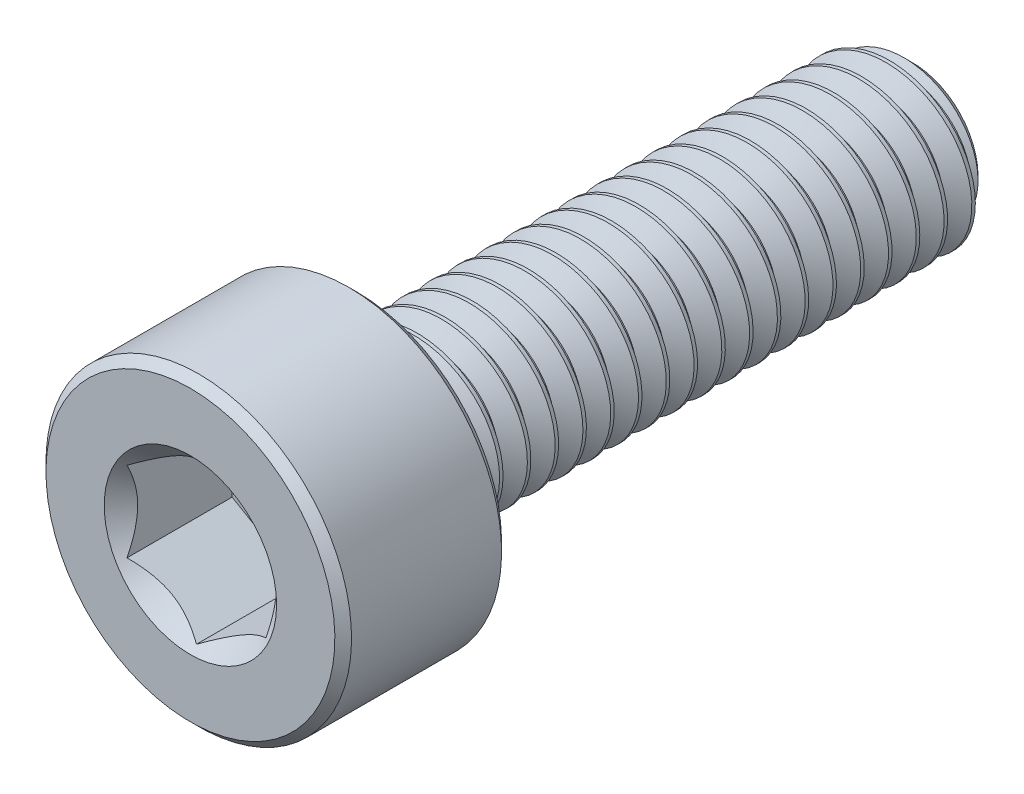
SolidWorks part; units mm, degrees
material "Alloy Steel"
ref_plane "Front Plane" through (0, 0, 0) normal (0, 0, 1) x (1, 0, 0)
ref_plane "Top Plane" through (0, 0, 0) normal (0, 1, 0) x (1, 0, 0)
ref_plane "Right Plane" through (0, 0, 0) normal (1, 0, 0) x (0, 0, -1)
sketch "Sketch1" plane through (0, 0, 0) normal (1, 0, 0) x (0, 0, -1)
  line L0 (-6.5, 0) -> (6.5, 0) construction
  line L1 (6.5, 0) -> (6.5, 1.1752) construction
  line L2 (6.5, 1.1752) -> (6.1752, 1.5) construction
  line L3 (6.1752, 1.5) -> (6.125, 1.5) construction
  line L4 (6.125, 1.5) -> (-3.5, 1.5) construction
  line L5 (-3.5, 1.5) -> (-3.5, 2.75) construction
  line L6 (-3.5, 2.75) -> (-6.5, 2.75) construction
  line L7 (-6.5, 2.75) -> (-6.5, 0) construction
  line L8 (6.5, 1.1752) -> (6.5, 1.5) construction
  line L9 (6.4688, 1.5541) -> (6.7188, 1.1211) construction
  line L10 (6.7188, 1.1211) -> (6.9687, 1.5541) construction
  line L11 (6.9687, 1.5541) -> (6.4688, 1.5541) construction
  line L12 (6.7188, 1.5541) -> (6.7188, 1.5) construction
  line L13 (6.7188, 1.1211) -> (6.7188, 1.1752) construction
  line L14 (6.6875, 1.1752) -> (6.75, 1.1752) construction
  line L15 (6.5, 1.5) -> (6.9375, 1.5) construction
  line L16 (6.4844, 1.5271) -> (6.9531, 1.5271) construction
  line L17 (6.5, 0) -> (6.5, -1.5) construction
  line L18 (-3.65, 2.75) -> (-3.5, 2.6) construction
  line L19 (-6.35, 2.75) -> (-6.5, 2.6) construction
  line L20 (-3.5, 1.5) -> (-3.5, 0) construction
  line L21 (-3.5, 0.75) -> (-0.1667, 0.75) construction
  line L22 (-0.1667, 0.75) -> (3.1667, 0.75) construction
  line L23 (3.1667, 0.75) -> (6.5, 0.75) construction
  line L24 (-0.1667, 0.75) -> (-0.1667, 1.5) construction
  line L25 (-0.1667, 1.5) -> (-0.1667, 2.75) construction
  line L26 (3.1667, 0.75) -> (3.1667, 2.75) construction
  point P0 (-6.5, 1.25)
  point P3 (5.25, 1.5)
  point P4 (0, 0)
  point P18 (3.1667, 1.5)
  point P22 (6.7188, 1.1752)
  point P24 (6.125, 1.5)
  point P25 (6.7188, 1.5)
  point P28 (6.7187, 1.5271)
  point P29 (5.25, -1.5)
  point P30 (-0.1667, 1.5)
  point P31 (-5, 2.75)
  point P37 (-4.025, 2.75)
  point P38 (-6.275, 2.75)
  point P45 (-0.1667, 0.75)
  point P46 (3.1667, 0.75)
  dimension "D2" = 0.0625
  dimension "D7" = 0.15
  dimension "D8" = 0.15
  dimension "D9" = 0.15
  dimension "D10" = 0.075
  dimension "D11" = 0.375
  dimension "Drive Size" = 2.5
  dimension "Head Diameter" = 5.5
  dimension "Head Height" = 3
  dimension "Thread Pitch" = 0.5
  dimension "Thread Dia" = 3
  dimension "Length" = 10
  dimension "D12" = 0.375
  dimension "D4" = 1.25
  dimension "D3" = 45
sketch "Sketch2" plane through (0, 0, 0) normal (1, 0, 0) x (0, 0, -1)
  line L0 (-6.5, 0) -> (-6.5, 2.6)
  line L1 (-6.35, 2.75) -> (-3.65, 2.75)
  line L2 (-3.5, 2.6) -> (-3.5, 1.65)
  line L4 (6.1752, 1.5) -> (6.5, 1.1752)
  line L5 (6.5, 1.1752) -> (6.5, 0)
  line L6 (-3.5, 2.75) -> (-6.5, 2.75) construction
  line L7 (6.5, 0) -> (-6.5, 0)
  line L8 (-6.35, 2.75) -> (-6.5, 2.6) construction
  line L10 (-6.35, 2.75) -> (-6.5, 2.6)
  line L14 (-3.65, 2.75) -> (-3.5, 2.6) construction
  line L16 (-3.65, 2.75) -> (-3.5, 2.6)
  line L17 (-3.5, 1.5) -> (-3.5, 2.75) construction
  line L19 (-3.35, 1.5) -> (6.1752, 1.5)
  line L20 (6.125, 1.5) -> (-3.5, 1.5) construction
  arc A1 (-3.5, 1.65) -> (-3.35, 1.5) centre (-3.35, 1.65) ccw
  dimension "D3" = 0.15
revolve "Revolve1" add sketch "Sketch2" angle 360 about L7
sketch "Sketch3" plane through (0, 0, 6.5) normal (0, 0, 1) x (1, 0, 0)
  line L1 (1.25, -0.7217) -> (1.25, 0.7217)
  line L2 (1.25, 0.7217) -> (0, 1.4434)
  line L3 (0, 1.4434) -> (-1.25, 0.7217)
  line L4 (-1.25, 0.7217) -> (-1.25, -0.7217)
  line L5 (-1.25, -0.7217) -> (0, -1.4434)
  line L6 (0, -1.4434) -> (1.25, -0.7217)
  circle A0 centre (0, 0) radius 1.25 construction
  circle A1 centre (0, 0) radius 2.75 construction
  circle A2 centre (0, 0) radius 2.75 construction
  circle A3 centre (0, 0) radius 1.4434 construction
  point P13 (0, 0)
  dimension "D1" = 2.8868
extrude "Cut-Extrude1" cut sketch "Sketch3" against normal offset from surface (2 mm away) 1 up to face at (0, 2.6, 3.5)
sketch "Sketch4" plane through (0, 0, 6.5) normal (0, 0, 1) x (1, 0, 0)
  circle A0 centre (0, 0) radius 1.5516
  dimension "D1" = 3.1033
extrude "Cut-Extrude2" cut sketch "Sketch4" against normal up to vertex (1.5 mm away) draft 45 up to point (0, 2.75, 5)
sketch "Sketch11" plane through (0, 0, 0) normal (1, 0, 0) x (0, 0, -1)
  line L0 (-6.5, 0) -> (6.5, 0) construction
  line L1 (-6.5, 0) -> (6.5, 0) construction
  line L2 (-1.625, 0) -> (-1.625, 1.5) construction
  line L3 (6.125, 1.5) -> (-3.5, 1.5) construction
  line L4 (4.625, 0) -> (4.625, 1.5) construction
  line L6 (6.5, 1.1752) -> (6.5, 1.5) construction
  point P2 (-1.625, 0)
  point P3 (4.625, 0)
  dimension "D1" = 1.875
  dimension "D2" = 1.875
sketch "Sketch6" plane through (0, 0, -6.5) normal (0, 0, -1) x (-1, 0, 0)
  circle A0 centre (0, 0) radius 1.5
curve "Helix/Spiral1" pitch 0.5 height 10.5 radius 1.5 centre (0, 0, -6.5) axis (0, 0, 1) start towards (0, 1, 0)
sketch "Sketch10" plane through (0, 0, 0) normal (1, 0, 0) x (0, 0, -1)
  line L0 (-3.35, -2.75) -> (-3.35, 2.75)
  line L5 (-6.5, 0) -> (6.5, 0) construction
  line L6 (-3.35, 1.5) -> (-3.35, -1.5) construction
  point P3 (-3.35, 0)
split "Split1" trim tools "Sketch10" bodies to split 106 resulting bodies 114 115
sketch "Sketch7" plane through (0, 0, 0) normal (1, 0, 0) x (0, 0, -1)
  line L0 (6.4844, 1.5271) -> (6.9531, 1.5271)
  line L1 (6.9531, 1.5271) -> (6.75, 1.1752)
  line L2 (6.75, 1.1752) -> (6.6875, 1.1752)
  line L3 (6.6875, 1.1752) -> (6.4844, 1.5271)
sweep "Cut-Sweep1" cut profiles "Sketch7" path "Helix/Spiral1" align with end faces yes
sketch "Sketch8" plane through (0, 0, 0) normal (1, 0, 0) x (0, 0, -1)
  line L0 (-3.5, 0) -> (-3.5, 1.5)
  line L1 (-3.35, -1.5) -> (-3.35, 1.5) construction
  line L2 (-3.5, 1.5) -> (-3.35, 1.5)
  line L4 (-3.35, 1.5) -> (-2.484, 0)
  line L5 (-2.484, 0) -> (-3.5, 0)
  line L6 (6.125, 1.5) -> (-3.5, 1.5) construction
  line L7 (-6.5, 0) -> (6.5, 0) construction
  dimension "D1" = 60
revolve "Revolve2" add sketch "Sketch8" angle 360 about L5
equation "\"D2@Sketch1\" = \"Thread Pitch@Sketch1\" / 8"
equation "\"D4@Helix/Spiral1\" = \"Thread Pitch@Sketch1\""
equation "\"D7@Sketch1\" = \"Head Height@Sketch1\" * .05"
equation "\"D8@Sketch1\"=\"D7@Sketch1\""
equation "\"D9@Sketch1\"=\"D7@Sketch1\""
equation "\"D10@Sketch1\"=\"D7@Sketch1\"/2"
equation "\"D11@Sketch1\"=\"D10@Sketch1\"*5"
equation "\"D4@Sketch1\"=\"Thread Pitch@Sketch1\"*2.5"
equation "\"D12@Sketch1\"=\"Thread Pitch@Sketch1\"*.75"
equation "\"D3@Helix/Spiral1\"=\"Length@Sketch1\"+\"Thread Pitch@Sketch1\""
equation "\"D3@Sketch2\"=\"Thread Dia@Sketch1\"*0.05"
equation "\"D1@Sketch11\"=\"Length@Sketch1\"*0.1875"
equation "\"D2@Sketch11\"=\"D1@Sketch11\""
equation "\"D1@Sketch4\"=\"D1@Sketch3\"*1.075"
